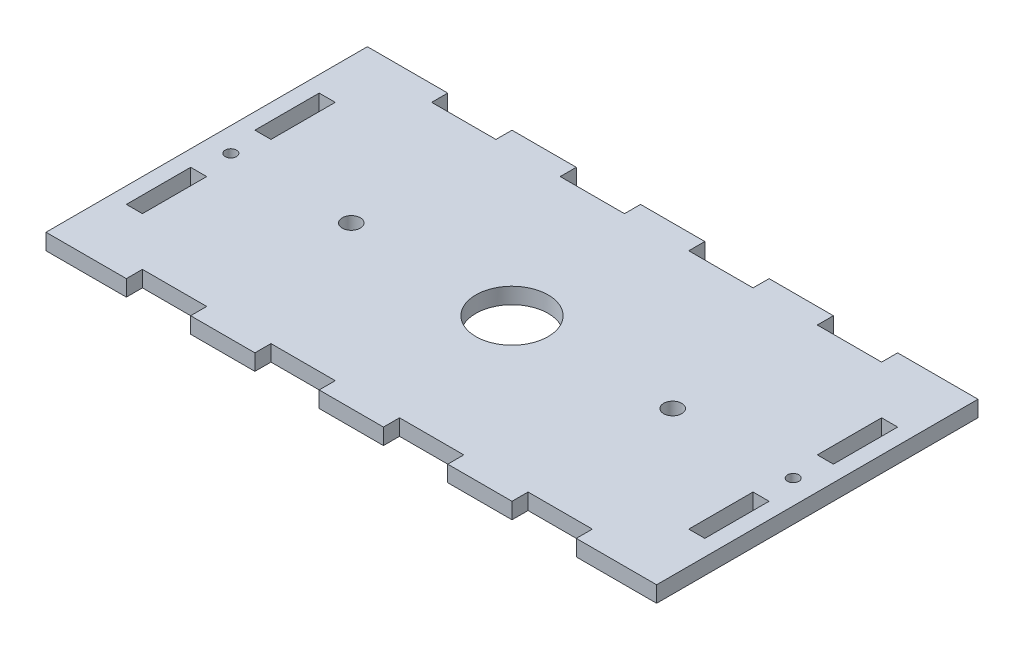
SolidWorks part; units mm, degrees
ref_plane "Front Plane" through (0, 0, 0) normal (0, 0, 1) x (1, 0, 0)
ref_plane "Top Plane" through (0, 0, 0) normal (0, 1, 0) x (1, 0, 0)
ref_plane "Right Plane" through (0, 0, 0) normal (1, 0, 0) x (0, 0, -1)
sketch "Sketch1" plane through (0, 0, 0) normal (0, 1, 0) x (1, 0, 0)
  line L1 (0, 0) -> (241.3, 0)
  line L2 (0, 0) -> (0, 127)
  line L3 (0, 127) -> (241.3, 127)
  line L4 (241.3, 0) -> (241.3, 127)
  dimension "D1" = 127
  dimension "D2" = 241.3
extrude "Boss-Extrude1" add sketch "Sketch1" along normal blind 6.35
sketch "Sketch13" plane through (0, 6.35, 0) normal (0, 1, 0) x (1, 0, 0)
  line L0 (0, 0) -> (241.3, 0) construction
  line L1 (31.75, 0) -> (57.15, 0)
  line L2 (31.75, 0) -> (31.75, 6.35)
  line L3 (31.75, 6.35) -> (57.15, 6.35)
  line L4 (57.15, 0) -> (57.15, 6.35)
  line L5 (82.55, 6.35) -> (107.95, 6.35)
  line L6 (107.95, 0) -> (107.95, 6.35)
  line L7 (82.55, 0) -> (107.95, 0)
  line L8 (82.55, 0) -> (82.55, 6.35)
  line L9 (133.35, 6.35) -> (158.75, 6.35)
  line L10 (158.75, 0) -> (158.75, 6.35)
  line L11 (133.35, 0) -> (158.75, 0)
  line L12 (133.35, 0) -> (133.35, 6.35)
  line L13 (184.15, 6.35) -> (209.55, 6.35)
  line L14 (209.55, 0) -> (209.55, 6.35)
  line L15 (184.15, 0) -> (209.55, 0)
  line L16 (184.15, 0) -> (184.15, 6.35)
  line L17 (31.75, 6.35) -> (82.55, 6.35) construction
  line L18 (0, 127) -> (0, 0) construction
  dimension "D1" = 25.4
  dimension "D2" = 6.35
  dimension "D4" = 50.8
  dimension "D5" = 31.75
  dimension "D3" = 4
extrude "Cut-Extrude6" cut sketch "Sketch13" against normal blind 6.35
pattern_linear "LPattern7" count 2 spacing 120.65 along (0, 0, -1) of "Cut-Extrude6"
sketch "Sketch14" plane through (0, 6.35, 0) normal (0, 1, 0) x (1, 0, 0)
  line L0 (0, 127) -> (0, 0) construction
  line L1 (6.35, 25.4) -> (12.7, 25.4)
  line L2 (6.35, 25.4) -> (6.35, 50.8)
  line L3 (6.35, 50.8) -> (12.7, 50.8)
  line L4 (12.7, 25.4) -> (12.7, 50.8)
  line L5 (0, 0) -> (31.75, 0) construction
  line L6 (228.6, 50.8) -> (234.95, 50.8)
  line L7 (228.6, 25.4) -> (228.6, 50.8)
  line L8 (234.95, 25.4) -> (234.95, 50.8)
  line L9 (228.6, 25.4) -> (234.95, 25.4)
  line L10 (228.6, 101.6) -> (234.95, 101.6)
  line L11 (228.6, 76.2) -> (228.6, 101.6)
  line L12 (234.95, 76.2) -> (234.95, 101.6)
  line L13 (228.6, 76.2) -> (234.95, 76.2)
  line L14 (6.35, 101.6) -> (12.7, 101.6)
  line L15 (6.35, 76.2) -> (6.35, 101.6)
  line L16 (12.7, 76.2) -> (12.7, 101.6)
  line L17 (6.35, 76.2) -> (12.7, 76.2)
  dimension "D1" = 25.4
  dimension "D2" = 6.35
  dimension "D3" = 6.35
  dimension "D4" = 25.4
  dimension "D5" = 2
  dimension "D6" = 2
extrude "Cut-Extrude7" cut sketch "Sketch14" against normal blind 6.35
hole_wizard "#8 Clearance Hole1" positions "Sketch16" profile "Sketch15" hole size "#8" standard "ANSI Inch"
sketch "Sketch16" plane through (0, 6.35, 0) normal (0, 1, 0) x (1, 0, 0)
  line L0 (12.7, 50.8) -> (6.35, 50.8) construction
  line L1 (6.35, 50.8) -> (6.35, 25.4) construction
  line L2 (234.95, 50.8) -> (228.6, 50.8) construction
  line L3 (228.6, 50.8) -> (228.6, 25.4) construction
  point P0 (9.525, 63.5)
  point P3 (9.525, 50.8)
  point P8 (231.775, 63.5)
  dimension "D1" = 12.7
  dimension "D2" = 3.175
  dimension "D3" = 12.7
  dimension "D4" = 3.175
sketch "Sketch15" plane through (9.525, 6.35, -63.5) normal (1, 0, 0) x (0, 0, 1)
  line L0 (0, 0) -> (0, 11.5107)
  line L1 (0, 11.5107) -> (2.2479, 10.16)
  line L2 (2.2479, 10.16) -> (2.2479, 0)
  line L5 (2.2479, 0) -> (0, 0)
  line L10 (0, 11.5107) -> (-2.2479, 10.16) construction
  line L11 (0, -6.35) -> (0, 107.95) construction
  dimension "Hole Dia." = 4.4958
  dimension "Hole Depth" = 10.16
  dimension "Drill Angle" = 118
sketch "Sketch18" plane through (0, 6.35, 0) normal (0, 1, 0) x (1, 0, 0)
  line L0 (0, 127) -> (0, 0) construction
  circle A0 centre (120.65, 63.5) radius 14.2875
  point P4 (0, 63.5)
  dimension "D1" = 28.575
  dimension "D2" = 120.65
extrude "Cut-Extrude9" cut sketch "Sketch18" against normal blind 7.62
sketch "Sketch19" plane through (0, 6.35, 0) normal (0, 1, 0) x (1, 0, 0)
  line L0 (0, 127) -> (0, 0) construction
  line L1 (241.3, 0) -> (241.3, 127) construction
  circle A0 centre (57.15, 63.5) radius 3.5719
  circle A1 centre (184.15, 63.5) radius 3.5719
  circle A2 centre (120.65, 63.5) radius 14.2875 construction
  point P8 (0, 63.5)
  point P11 (241.3, 63.5)
  dimension "D1" = 7.1437
  dimension "D2" = 7.1437
  dimension "D3" = 63.5
  dimension "D4" = 63.5
extrude "Cut-Extrude10" cut sketch "Sketch19" against normal blind 7.62
equation "\"THICK\"= .25"
